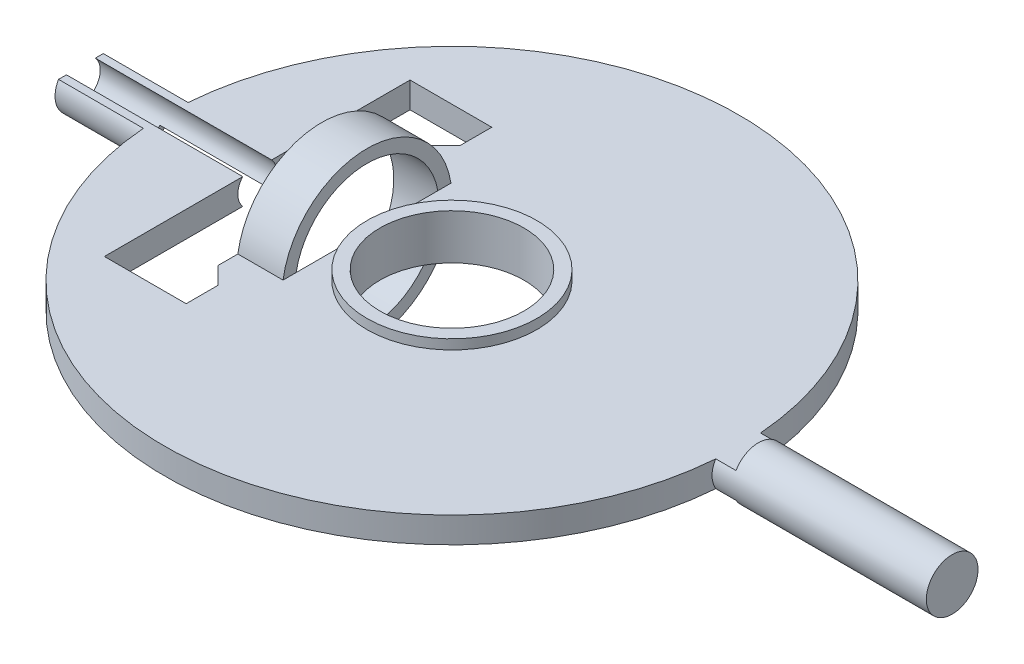
SolidWorks part; units mm, degrees
ref_plane "Front Plane" through (0, 0, 0) normal (0, 0, 1) x (1, 0, 0)
ref_plane "Top Plane" through (0, 0, 0) normal (0, 1, 0) x (1, 0, 0)
ref_plane "Right Plane" through (0, 0, 0) normal (1, 0, 0) x (0, 0, -1)
sketch "Sketch1" plane through (0, 0, 0) normal (0, 1, 0) x (1, 0, 0)
  circle A1 centre (0, 0) radius 44.45
  dimension "D1" = 88.9
extrude "Boss-Extrude1" add sketch "Sketch1" along normal mid plane 4
sketch "Sketch5" plane through (0, 0, 0) normal (0, 1, 0) x (1, 0, 0)
  circle A0 centre (0, 0) radius 11.15
  circle A1 centre (0, 0) radius 13.15
  dimension "D1" = 22.3
  dimension "D2" = 2
extrude "Boss-Extrude2" add sketch "Sketch5" along normal mid plane 7
extrude "Cut-Extrude2" cut sketch "Sketch5<2>" against normal through all both and the other way through all contours A0 region at (0, 0, 0)
sketch "Sketch5<2>" plane through (0, 0, 0) normal (0, 1, 0) x (1, 0, 0) same geometry as "Sketch5"
sketch "Sketch6" plane through (0, 0, 0) normal (0, 1, 0) x (1, 0, 0)
  line L0 (-1000, 0) -> (49000, 0) construction
  line L1 (0, 0) -> (0, 69.0003) construction
  line L2 (-47.45, 4) -> (-47.45, -4)
  line L3 (-47.45, 4) -> (-44.2697, 4)
  line L4 (-47.45, -4) -> (-44.2697, -4)
  line L5 (47.45, -4) -> (44.2697, -4)
  line L6 (47.45, 4) -> (47.45, -4)
  line L7 (47.45, 4) -> (44.2697, 4)
  circle A0 centre (0, 0) radius 47.45 construction
  circle A1 centre (0, 0) radius 44.45 construction
  circle A2 centre (0, 0) radius 44.45
  point P11 (-47.45, 0)
  dimension "D1" = 3
  dimension "D2" = 8
extrude "Boss-Extrude4" add sketch "Sketch6" along normal mid plane 4 contours A2 L3 L2 L4 | A2 L5 L6 L7 region at (-45.9195, 0, 0) region at (45.9195, 0, 0)
sketch "Sketch7" plane through (-47.45, 0, 0) normal (-1, 0, 0) x (0, 0, 1)
  circle A0 centre (0, 0) radius 4
  dimension "D1" = 8
extrude "Cut-Extrude-Thin1" cut sketch "Sketch7" against normal up to surface (3.7258 mm away) thin contours A0 up to face at (0, 0, -24.225) thin type one direction wall 4
extrude "Boss-Extrude6" add sketch "Sketch7<3>" along normal blind 30 contours A0
sketch "Sketch7<3>" plane through (-47.45, 0, 0) normal (-1, 0, 0) x (0, 0, 1) same geometry as "Sketch7"
mirror "Mirror2" about plane through (0, 0, 0) normal (1, 0, 0) of "Cut-Extrude-Thin1"
sketch "Sketch11" plane through (47.45, 0, 0) normal (1, 0, 0) x (0, 0, -1)
  circle A0 centre (0, 0) radius 4
  dimension "D1" = 8
extrude "Boss-Extrude7" add sketch "Sketch11" along normal blind 30
sketch "Sketch13" plane through (-77.45, 0, 0) normal (-1, 0, 0) x (0, 0, 1)
  circle A0 centre (0, 0) radius 3
  circle A1 centre (0, 0) radius 4 construction
  dimension "D1" = 6
extrude "Cut-Extrude3" cut sketch "Sketch13" against normal up to surface (64.6468 mm away) up to face at (0, 2, 13.15)
ref_plane "Plane1" through (-13.15, 0, 0) normal (-1, 0, 0) x (0, 0, 1)
sketch "Sketch15" plane through (-13.15, 0, 0) normal (-1, 0, 0) x (0, 0, 1)
  circle A0 centre (0, 0) radius 13.15
  circle A1 centre (0, 0) radius 11.15
  dimension "D1" = 22.3
  dimension "D2" = 2
extrude "Boss-Extrude8" add sketch "Sketch15" along normal blind 7
extrude "Cut-Extrude4" cut sketch "Sketch15<2>" along normal blind 17 contours A1
sketch "Sketch15<2>" plane through (-13.15, 0, 0) normal (-1, 0, 0) x (0, 0, 1) same geometry as "Sketch15"
sketch "Sketch20" plane through (0, 0, 0) normal (0, 1, 0) x (1, 0, 0)
  line L0 (-5.0299, -12.15) -> (-20.15, -12.15) construction
  line L1 (-20.15, 12.997) -> (-20.15, -12.997) construction
  line L2 (-20.15, -12.15) -> (-20.15, -16.0509)
  line L3 (-20.15, -16.0509) -> (-17.4893, -18.7116)
  line L4 (-20.15, -16.0509) -> (-21.4053, -17.3063) construction
  line L5 (-17.4893, -23.6615) -> (-30.15, -23.6615)
  line L6 (-30.15, -23.6615) -> (-30.15, 23.6615)
  line L7 (-20.15, -12.15) -> (-20.15, 0)
  line L8 (0, 0) -> (3.3862, 0) construction
  line L9 (-20.15, 16.0509) -> (-17.4893, 18.7116)
  line L10 (-17.4893, 23.6615) -> (-30.15, 23.6615)
  line L11 (-20.15, 12.15) -> (-20.15, 16.0509)
  line L12 (-5.0299, 12.15) -> (-20.15, 12.15) construction
  line L13 (-20.15, 12.15) -> (-20.15, 0)
  line L14 (-30.15, -2.2361) -> (-30.15, -10.9692) construction
  line L15 (-17.4893, -23.6615) -> (-17.4893, -18.7116)
  line L16 (-17.4893, 23.6615) -> (-17.4893, 18.7116)
  circle A0 centre (0, 0) radius 13.15 construction
  point P20 (-30.15, 0)
  dimension "D1" = 12.15
  dimension "D2" = 135
  dimension "D3" = 90
extrude "Cut-Extrude8" cut sketch "Sketch20" against normal through all both and the other way through all
sketch "Sketch23" plane through (-47.45, 0, 0) normal (1, 0, 0) x (0, 0, -1)
  line L4 (-3.4641, 2) -> (-2.2361, 2)
  line L5 (2.2361, 2) -> (3.4641, 2)
  line L6 (-3.4641, 2) -> (-2.2361, 2)
  line L7 (2.2361, 2) -> (3.4641, 2)
  arc A4 (2.2361, 2) -> (-2.2361, 2) centre (0, 0) ccw
  arc A5 (3.4641, 2) -> (-3.4641, 2) centre (0, 0) ccw
  arc A6 (2.2361, 2) -> (-2.2361, 2) centre (0, 0) ccw
  arc A7 (3.4641, 2) -> (-3.4641, 2) centre (0, 0) ccw
  dimension "D1" = 0
extrude "Cut-Extrude9" cut sketch "Sketch23" against normal through all
sketch "Sketch24" plane through (-77.45, 0, 0) normal (-1, 0, 0) x (0, 0, 1)
  line L4 (-2.2361, 2) -> (-3.4641, 2)
  line L5 (3.4641, 2) -> (2.2361, 2)
  line L6 (-2.2361, 2) -> (-3.4641, 2)
  line L7 (3.4641, 2) -> (2.2361, 2)
  arc A4 (-3.4641, 2) -> (3.4641, 2) centre (0, 0) ccw
  arc A5 (-2.2361, 2) -> (2.2361, 2) centre (0, 0) ccw
  arc A6 (-3.4641, 2) -> (3.4641, 2) centre (0, 0) ccw
  arc A7 (-2.2361, 2) -> (2.2361, 2) centre (0, 0) ccw
  dimension "D1" = 0
extrude "Cut-Extrude10" cut sketch "Sketch24" against normal blind 20
